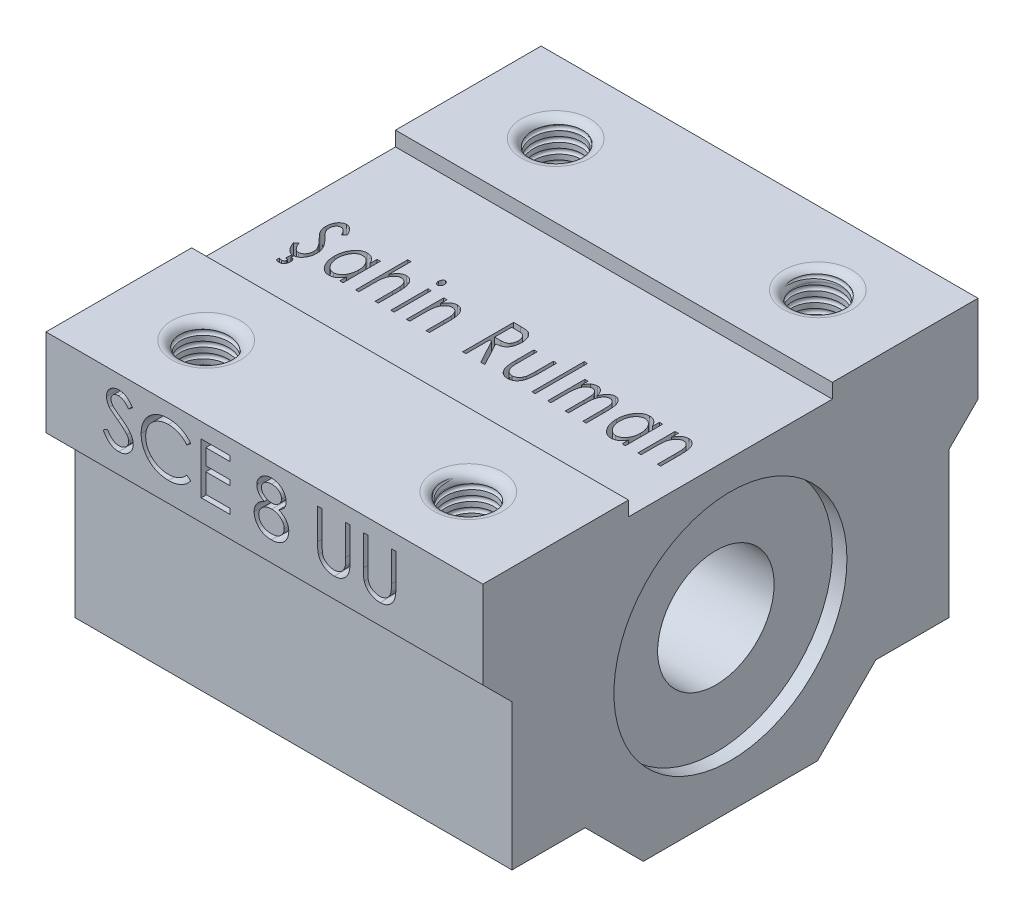
SolidWorks part; units mm, degrees
ref_plane "Front Plane" through (0, 0, 0) normal (0, 0, 1) x (1, 0, 0)
ref_plane "Top Plane" through (0, 0, 0) normal (0, 1, 0) x (1, 0, 0)
ref_plane "Right Plane" through (0, 0, 0) normal (1, 0, 0) x (0, 0, -1)
sketch "Sketch1" plane through (0, 0, 0) normal (1, 0, 0) x (0, 0, -1)
  line L0 (-17, 22) -> (-7, 22)
  line L1 (-5.9801, 0) -> (5.9801, 0)
  line L2 (5.9801, 0) -> (9.9801, 4)
  line L3 (9.9801, 4) -> (15, 4)
  line L4 (15, 4) -> (15, 14)
  line L5 (15, 14) -> (17, 16)
  line L6 (17, 16) -> (17, 22)
  line L7 (0, 0) -> (0, 32.3281) construction
  line L8 (-5.9801, 0) -> (-9.9801, 4)
  line L9 (-9.9801, 4) -> (-15, 4)
  line L10 (-15, 4) -> (-15, 14)
  line L11 (-15, 14) -> (-17, 16)
  line L12 (-17, 16) -> (-17, 22)
  line L17 (-7, 21) -> (7, 21)
  line L18 (-7, 21) -> (-7, 22)
  line L21 (7, 21) -> (7, 22)
  line L22 (7, 22) -> (17, 22)
  dimension "D1" = 34
  dimension "D2" = 17
  dimension "D3" = 22
  dimension "D4" = 18
  dimension "D5" = 2
  dimension "D6" = 2
  dimension "D7" = 6
  dimension "D8" = 4
  dimension "D9" = 6
  dimension "D10" = 18
  dimension "D15" = 1
extrude "Boss-Extrude1" add sketch "Sketch1" along normal mid plane 30
sketch "Sketch2" plane through (15, 0, 0) normal (1, 0, 0) x (0, 0, -1)
  line L0 (-18.9525, 22) -> (20.4204, 22) construction
  circle A0 centre (0, 11) radius 4
extrude "Cut-Extrude1" cut sketch "Sketch2" against normal through all
sketch "Sketch3" plane through (0, 22, 0) normal (0, 1, 0) x (1, 0, 0)
  circle A0 centre (-9, 12) radius 1.65
  circle A1 centre (9, 12) radius 1.65
  circle A2 centre (9, -12) radius 1.65
  circle A3 centre (-9, -12) radius 1.65
  dimension "D5" = 3.3
extrude "Cut-Extrude2" cut sketch "Sketch3" against normal through all
fillet "Fillet1" radius 0.7 4 edges at (-9, 22, -10.35) (9, 22, -10.35) (9, 22, 13.65) (-9, 22, 13.65)
sketch "Sketch4" plane through (0, 22, 0) normal (0, 1, 0) x (1, 0, 0)
  circle A0 centre (-9, -12) radius 1.65
curve "Helix/Spiral1" pitch 0.7 height 8 turns 11.4286
ref_plane "Plane1" through (0, 0, 10.8333) normal (0, 0, 1) x (1, 0, 0)
sketch "Sketch5" plane through (0, 0, 10.8333) normal (0, 0, 1) x (1, 0, 0)
  circle A0 centre (-10.1667, 22) radius 0.175
  spline S0 degree 3 poles (-10.1667, 22) (-10.0143, 21.9854) (-9.6447, 21.956) (-8.9939, 21.9121) (-8.3433, 21.8681) (-7.7938, 21.8242) (-7.4296, 21.7802) (-7.3067, 21.7363) (-7.4441, 21.6923) (-7.8205, 21.6484) (-8.3781, 21.6044) (-9.0313, 21.5604) (-9.6797, 21.5165) (-10.2237, 21.4725) (-10.5796, 21.4286) (-10.6928, 21.3846) (-10.5459, 21.3407) (-10.1614, 21.2967) (-9.5985, 21.2527) (-8.9436, 21.2088) (-8.2974, 21.1648) (-7.7591, 21.1209) (-7.4116, 21.0769) (-7.308, 21.033) (-7.4645, 20.989) (-7.8569, 20.9451) (-8.425, 20.9011) (-9.0814, 20.8571) (-9.7253, 20.8132) (-10.2578, 20.7692) (-10.597, 20.7253) (-10.6908, 20.6813) (-10.5248, 20.6374) (-10.1245, 20.5934) (-9.5514, 20.5495) (-8.8936, 20.5055) (-8.2521, 20.4615) (-7.7256, 20.4176) (-7.3949, 20.3736) (-7.3108, 20.3297) (-7.4863, 20.2857) (-7.8944, 20.2418) (-8.4724, 20.1978) (-9.1314, 20.1538) (-9.7703, 20.1099) (-10.2908, 20.0659) (-10.6129, 20.022) (-10.6872, 19.978) (-10.5023, 19.9341) (-10.0865, 19.8901) (-9.5038, 19.8462) (-8.8436, 19.8022) (-8.2075, 19.7582) (-7.6932, 19.7143) (-7.3796, 19.6703) (-7.3151, 19.6264) (-7.5094, 19.5824) (-7.9328, 19.5385) (-8.5202, 19.4945) (-9.1813, 19.4505) (-9.8145, 19.4066) (-10.3226, 19.3626) (-10.6275, 19.3187) (-10.6822, 19.2747) (-10.4785, 19.2308) (-10.0476, 19.1868) (-9.4557, 19.1429) (-8.7938, 19.0989) (-8.1636, 19.0549) (-7.6619, 19.011) (-7.3658, 18.967) (-7.3208, 18.9231) (-7.5338, 18.8791) (-7.9722, 18.8352) (-8.5685, 18.7912) (-9.231, 18.7473) (-9.8581, 18.7033) (-10.3533, 18.6593) (-10.6406, 18.6154) (-10.6758, 18.5714) (-10.4535, 18.5275) (-10.0078, 18.4835) (-9.4073, 18.4396) (-8.7442, 18.3956) (-8.1204, 18.3516) (-7.6318, 18.3077) (-7.3534, 18.2637) (-7.328, 18.2198) (-7.5596, 18.1758) (-8.0124, 18.1319) (-8.6171, 18.0879) (-9.2806, 18.044) (-9.9009, 18) (-10.3829, 17.956) (-10.6523, 17.9121) (-10.6678, 17.8681) (-10.4271, 17.8242) (-9.9671, 17.7802) (-9.3585, 17.7363) (-8.6948, 17.6923) (-8.078, 17.6484) (-7.6028, 17.6044) (-7.3424, 17.5604) (-7.3367, 17.5165) (-7.5865, 17.4725) (-8.0536, 17.4286) (-8.6661, 17.3846) (-9.3298, 17.3407) (-9.943, 17.2967) (-10.4112, 17.2527) (-10.6625, 17.2088) (-10.6584, 17.1648) (-10.3995, 17.1209) (-9.9255, 17.0769) (-9.3093, 17.033) (-8.6456, 16.989) (-8.0363, 16.9451) (-7.5751, 16.9011) (-7.3329, 16.8571) (-7.3468, 16.8132) (-7.6147, 16.7692) (-8.0955, 16.7253) (-8.7153, 16.6813) (-9.3788, 16.6374) (-9.9842, 16.5934) (-10.4382, 16.5495) (-10.6713, 16.5055) (-10.6476, 16.4615) (-10.3707, 16.4176) (-9.8832, 16.3736) (-9.26, 16.3297) (-8.5968, 16.2857) (-7.9956, 16.2418) (-7.5487, 16.1978) (-7.3248, 16.1538) (-7.3584, 16.1099) (-7.6442, 16.0659) (-8.1383, 16.022) (-8.7648, 15.978) (-9.4275, 15.9341) (-10.0245, 15.8901) (-10.4641, 15.8462) (-10.6787, 15.8022) (-10.6353, 15.7582) (-10.3407, 15.7143) (-9.84, 15.6703) (-9.2103, 15.6264) (-8.5483, 15.5824) (-7.9557, 15.5385) (-7.5235, 15.4945) (-7.3182, 15.4505) (-7.3714, 15.4066) (-7.6748, 15.3626) (-8.1818, 15.3187) (-8.8146, 15.2747) (-9.4758, 15.2308) (-10.0639, 15.1868) (-10.4886, 15.1429) (-10.6845, 15.0989) (-10.6216, 15.0549) (-10.3095, 15.011) (-9.7962, 14.967) (-9.1605, 14.9231) (-8.5002, 14.8791) (-7.9167, 14.8352) (-7.4996, 14.7912) (-7.3131, 14.7473) (-7.3858, 14.7033) (-7.7065, 14.6593) (-8.226, 14.6154) (-8.8644, 14.5714) (-9.5237, 14.5275) (-10.1025, 14.4835) (-10.5118, 14.4396) (-10.6889, 14.3956) (-10.6064, 14.3516) (-10.2771, 14.3077) (-9.7516, 14.2637) (-9.1106, 14.2198) (-8.4526, 14.1758) (-7.8786, 14.1319) (-7.4771, 14.0879) (-7.3093, 14.044) (-7.3714, 14.0146) (-7.4426, 14) knots 0 0 0 0 0.005495 0.010989 0.016484 0.021978 0.027473 0.032967 0.038462 0.043956 0.049451 0.054945 0.06044 0.065934 0.071429 0.076923 0.082418 0.087912 0.093407 0.098901 0.104396 0.10989 0.115385 0.120879 0.126374 0.131868 0.137363 0.142857 0.148352 0.153846 0.159341 0.164835 0.17033 0.175824 0.181319 0.186813 0.192308 0.197802 0.203297 0.208791 0.214286 0.21978 0.225275 0.230769 0.236264 0.241758 0.247253 0.252747 0.258242 0.263736 0.269231 0.274725 0.28022 0.285714 0.291209 0.296703 0.302198 0.307692 0.313187 0.318681 0.324176 0.32967 0.335165 0.340659 0.346154 0.351648 0.357143 0.362637 0.368132 0.373626 0.379121 0.384615 0.39011 0.395604 0.401099 0.406593 0.412088 0.417582 0.423077 0.428571 0.434066 0.43956 0.445055 0.450549 0.456044 0.461538 0.467033 0.472527 0.478022 0.483516 0.489011 0.494505 0.5 0.505495 0.510989 0.516484 0.521978 0.527473 0.532967 0.538462 0.543956 0.549451 0.554945 0.56044 0.565934 0.571429 0.576923 0.582418 0.587912 0.593407 0.598901 0.604396 0.60989 0.615385 0.620879 0.626374 0.631868 0.637363 0.642857 0.648352 0.653846 0.659341 0.664835 0.67033 0.675824 0.681319 0.686813 0.692308 0.697802 0.703297 0.708791 0.714286 0.71978 0.725275 0.730769 0.736264 0.741758 0.747253 0.752747 0.758242 0.763736 0.769231 0.774725 0.78022 0.785714 0.791209 0.796703 0.802198 0.807692 0.813187 0.818681 0.824176 0.82967 0.835165 0.840659 0.846154 0.851648 0.857143 0.862637 0.868132 0.873626 0.879121 0.884615 0.89011 0.895604 0.901099 0.906593 0.912088 0.917582 0.923077 0.928571 0.934066 0.93956 0.945055 0.950549 0.956044 0.961538 0.967033 0.972527 0.978022 0.983516 0.989011 0.994505 1 1 1 1 construction
  dimension "D1" = 0.35
sweep "Cut-Sweep1" cut profiles "Sketch5" path "Helix/Spiral1"
mirror "Mirror1" about plane through (0, 0, 0) normal (0, 0, 1) of "Cut-Sweep1"
mirror "Mirror2" about plane through (0, 0, 0) normal (1, 0, 0) of "Mirror1", "Cut-Sweep1"
sketch "Sketch6" plane through (0, 21, 0) normal (0, 1, 0) x (1, 0, 0)
  text T0 "Şahin Rulman" font "Century Gothic" height 3.5
extrude "Cut-Extrude3" cut sketch "Sketch6" against normal blind 2
sketch "Sketch7" plane through (0, 0, 17) normal (0, 0, 1) x (1, 0, 0)
  text T0 "SCE 8 UU"
extrude "Cut-Extrude4" cut sketch "Sketch7" against normal blind 2
sketch "Sketch8" plane through (15, 0, 0) normal (1, 0, 0) x (0, 0, -1)
  circle A0 centre (0, 11) radius 8
  dimension "D1" = 16
extrude "Cut-Extrude5" cut sketch "Sketch8" against normal blind 1
mirror "Mirror3" about plane through (0, 0, 0) normal (1, 0, 0) of "Cut-Extrude5"
